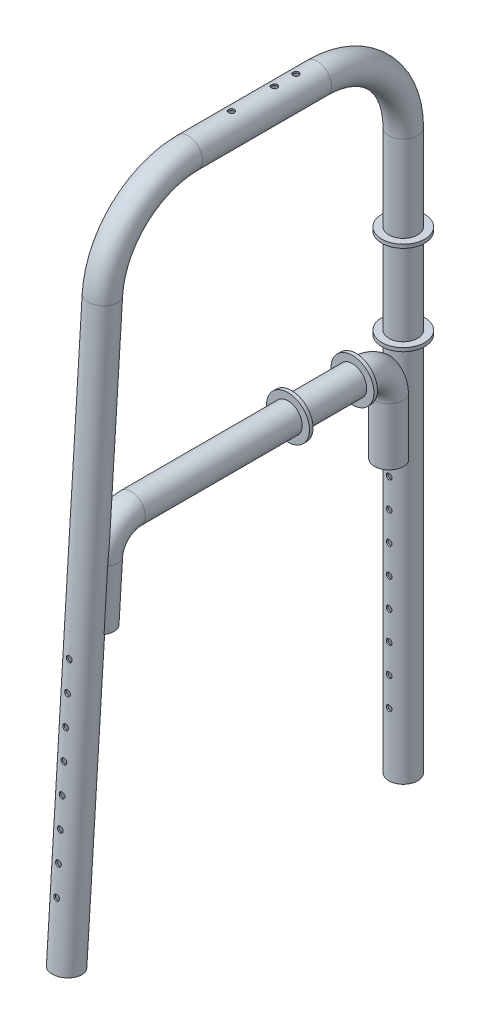
SolidWorks part; units mm, degrees
ref_plane "Front Plane" through (0, 0, 0) normal (0, 0, 1) x (1, 0, 0)
ref_plane "Top Plane" through (0, 0, 0) normal (0, 1, 0) x (1, 0, 0)
ref_plane "Right Plane" through (0, 0, 0) normal (1, 0, 0) x (0, 0, -1)
sketch "Sketch1" plane through (0, 0, 0) normal (1, 0, 0) x (0, 0, -1)
  line L0 (0, 0) -> (0, 900) construction
  line L1 (-237.1354, 0) -> (-187.1354, 787.6027)
  line L2 (-67.3765, 900) -> (112.8646, 900)
  line L3 (232.8646, 780) -> (232.8646, 0)
  arc A0 (-67.3765, 900) -> (-187.1354, 787.6027) centre (-67.3765, 780) ccw
  arc A1 (232.8646, 780) -> (112.8646, 900) centre (112.8646, 780) ccw
  point P9 (-180, 900)
  point P12 (232.8646, 900)
  dimension "D6" = 120
  dimension "D7" = 120
  dimension "D1" = 470
  dimension "D2" = 420
  dimension "D4" = 180
  dimension "D5" = 900
ref_plane "Plane1" through (0, 0, 237.1354) normal (0, 0.998, -0.0634) x (1, 0, 0)
sketch "Sketch40" plane through (0, 0, 237.1354) normal (0, 0.998, -0.0634) x (1, 0, 0)
  circle A0 centre (0, 0) radius 20
  circle A1 centre (0, 0) radius 18
  dimension "D2" = 40
  dimension "D1" = 2
sweep "Sweep2" add profiles "Sketch40" path "Sketch1"
sketch "Sketch15" plane through (0, 0, 0) normal (1, 0, 0) x (0, 0, -1)
  line L0 (-192.1756, 392.5342) -> (-187.0969, 472.5342)
  line L1 (-217.1756, -1.2671) -> (-167.1756, 786.3356) construction
  line L2 (-147.1772, 510) -> (172.8646, 510)
  line L3 (212.8646, 780) -> (212.8646, 0) construction
  line L4 (212.8646, 470) -> (212.8646, 390)
  arc A0 (212.8646, 470) -> (172.8646, 510) centre (172.8646, 470) ccw
  arc A1 (-147.1772, 510) -> (-187.0969, 472.5342) centre (-147.1772, 470) ccw
  point P10 (212.8646, 510)
  point P13 (-184.7184, 510)
  dimension "D1" = 40
  dimension "D2" = 80
ref_plane "Plane2" through (0, 392.5342, 192.1756) normal (0, 0.998, -0.0634) x (1, 0, 0)
sketch "Sketch45" plane through (0, 392.5342, 192.1756) normal (0, 0.998, -0.0634) x (1, 0, 0)
  circle A0 centre (0, 0) radius 20
  circle A1 centre (0, 0) radius 18
  dimension "D2" = 40
  dimension "D1" = 2
sweep "Sweep3" add profiles "Sketch45" path "Sketch15"
sweep "Cut-Sweep1" cut path "Sketch1<3>" circular profile diameter 40 parameters "D3"=40
sketch "Sketch1<3>" plane through (0, 0, 0) normal (1, 0, 0) x (0, 0, -1) same geometry as "Sketch1"
combine bodies "Combine1" operation type add bodies to combine 102 110
sketch "Sketch22" plane through (0, 0, 0) normal (0, 0, 1) x (1, 0, 0)
  line L0 (0, 0) -> (0, 368) construction
  circle A0 centre (0, 368) radius 4
  circle A1 centre (0, 328) radius 4
  circle A2 centre (0, 288) radius 4
  circle A3 centre (0, 248) radius 4
  circle A4 centre (0, 208) radius 4
  circle A5 centre (0, 168) radius 4
  circle A6 centre (0, 128) radius 4
  circle A7 centre (0, 88) radius 4
  ellipse E0 centre (0, 0) end of major axis (20, 0) minor radius 1.2671 construction
  dimension "D1" = 8
  dimension "D2" = 8
  dimension "D3" = 88
  dimension "D4" = 40
extrude "Cut-Extrude1" cut sketch "Sketch22" against normal up to next
sketch "Sketch59" plane through (0, 0, 0) normal (1, 0, 0) x (0, 0, -1)
  line L0 (212.8646, 655) -> (212.8646, 535) construction
  line L1 (212.8646, 780) -> (212.8646, 514.7214) construction
  line L2 (212.8646, 0) -> (252.8646, 0) construction
  line L3 (212.8646, 655) -> (202.8646, 655)
  line L4 (212.8646, 655) -> (212.8646, 660)
  line L5 (212.8646, 660) -> (202.8646, 660)
  line L6 (202.8646, 655) -> (202.8646, 660)
  line L7 (212.8646, 535) -> (202.8646, 535)
  line L8 (212.8646, 535) -> (212.8646, 530)
  line L9 (212.8646, 530) -> (202.8646, 530)
  line L10 (202.8646, 535) -> (202.8646, 530)
  line L11 (232.8646, 0) -> (232.8646, 780) construction
  line L12 (252.8646, 780) -> (212.8646, 780) construction
  line L13 (172.8646, 530) -> (-147.1772, 530) construction
  dimension "D2" = 5
  dimension "D3" = 10
  dimension "D4" = 120
revolve "Revolve1" add sketch "Sketch59" angle 360 about L11
sketch "Sketch66" plane through (0, 0, 0) normal (1, 0, 0) x (0, 0, -1)
  line L0 (172.8646, 530) -> (-147.1772, 530) construction
  line L3 (161.8646, 530) -> (166.8646, 530)
  line L4 (161.8646, 530) -> (161.8646, 540)
  line L5 (161.8646, 540) -> (166.8646, 540)
  line L6 (166.8646, 530) -> (166.8646, 540)
  line L7 (172.8646, 530) -> (172.8646, 490) construction
  line L8 (71.8646, 530) -> (76.8646, 530)
  line L9 (71.8646, 530) -> (71.8646, 540)
  line L10 (71.8646, 540) -> (76.8646, 540)
  line L11 (76.8646, 530) -> (76.8646, 540)
  line L12 (172.8646, 510) -> (-147.1772, 510) construction
  line L13 (-147.1772, 530) -> (-147.1772, 490) construction
  dimension "D1" = 10
  dimension "D2" = 5
  dimension "D3" = 85
  dimension "D4" = 96
revolve "Revolve2" add sketch "Sketch66" angle 360 about L12
ref_plane "Plane6" through (0, 920, 0) normal (0, 1, 0) x (1, 0, 0)
sketch "Sketch71" plane through (0, 920, 0) normal (0, 1, 0) x (1, 0, 0)
  line L0 (0, 0) -> (0, 112.8646) construction
  line L1 (-20, 112.8646) -> (20, 112.8646) construction
  line L2 (-80.5396, 22.8646) -> (125.9362, 22.8646) construction
  circle A0 centre (0, 52.8646) radius 4.2
  circle A1 centre (0, -7.1354) radius 4.2
  circle A2 centre (0, 82.8646) radius 4.2
  dimension "D4" = 8.4
  dimension "D5" = 30
  dimension "D2" = 60
  dimension "D3" = 30
extrude "Cut-Extrude3" cut sketch "Sketch71" against normal blind 40
ref_plane "Plane7" through (0, 13.7267, 216.2237) normal (0, -0.0634, -0.998) x (-1, 0, 0)
sketch "Sketch73" plane through (0, 13.7267, 216.2237) normal (0, -0.0634, -0.998) x (-1, 0, 0)
  line L1 (0, -15.2215) -> (0, 74.976) construction
  circle A0 centre (0, 74.976) radius 4
  circle A1 centre (0, 114.976) radius 4
  circle A2 centre (0, 154.976) radius 4
  circle A3 centre (0, 194.976) radius 4
  circle A4 centre (0, 234.976) radius 4
  circle A5 centre (0, 274.976) radius 4
  circle A6 centre (0, 314.976) radius 4
  circle A7 centre (0, 354.976) radius 4
  dimension "D4" = 8
  dimension "D1" = 90
  dimension "D3" = 40
  dimension "D2" = 8
extrude "Cut-Extrude4" cut sketch "Sketch73" against normal through all
